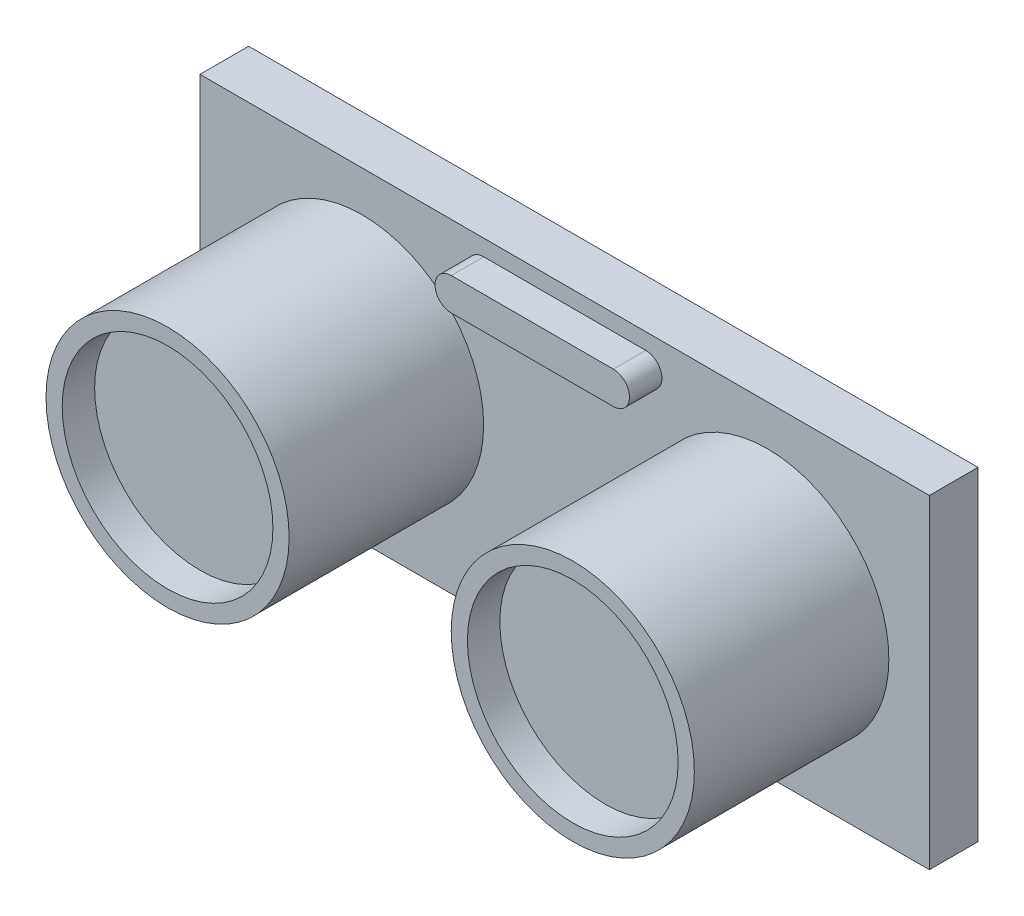
SolidWorks part; units mm, degrees
ref_plane "Front Plane" through (0, 0, 0) normal (0, 0, 1) x (1, 0, 0)
ref_plane "Top Plane" through (0, 0, 0) normal (0, 1, 0) x (1, 0, 0)
ref_plane "Right Plane" through (0, 0, 0) normal (1, 0, 0) x (0, 0, -1)
sketch "Sketch1" plane through (0, 0, 0) normal (0, 0, 1) x (1, 0, 0)
  line L1 (0, 0) -> (45, 0)
  line L2 (0, 0) -> (0, 20)
  line L3 (0, 20) -> (45, 20)
  line L4 (45, 0) -> (45, 20)
  dimension "D1" = 45
  dimension "D2" = 20
extrude "Boss-Extrude1" add sketch "Sketch1" along normal blind 3
sketch "Sketch2" plane through (0, 0, 3) normal (0, 0, 1) x (1, 0, 0)
  line L0 (45, 0) -> (45, 20) construction
  circle A0 centre (10, 10) radius 7.5
  circle A1 centre (35, 10) radius 7.5
  circle A2 centre (10, 10) radius 6.5
  circle A3 centre (35, 10) radius 6.5
  dimension "D3" = 15
  dimension "D4" = 15
  dimension "D6" = 13
  dimension "D7" = 13
  dimension "D1" = 10
  dimension "D2" = 10
  dimension "D5" = 10
extrude "Boss-Extrude2" add sketch "Sketch2" along normal blind 12
extrude "Boss-Extrude3" add sketch "Sketch2<2>" along normal blind 10 contours A2 | A3 region at (10, 10, 3) region at (35, 10, 3)
sketch "Sketch2<2>" plane through (0, 0, 3) normal (0, 0, 1) x (1, 0, 0) same geometry as "Sketch2"
sketch "Sketch3" plane through (0, 0, 3) normal (0, 0, 1) x (1, 0, 0)
  line L0 (17.5, 18) -> (27.5, 18) construction
  line L1 (17.5, 19) -> (27.5, 19)
  line L2 (17.5, 17) -> (27.5, 17)
  line L3 (45, 20) -> (0, 20) construction
  arc A0 (17.5, 19) -> (17.5, 17) centre (17.5, 18) ccw
  arc A1 (27.5, 17) -> (27.5, 19) centre (27.5, 18) ccw
  point P2 (22.5, 18)
  dimension "D1" = 22.5
  dimension "D2" = 10
  dimension "D3" = 2
  dimension "D4" = 2
extrude "Boss-Extrude4" add sketch "Sketch3" along normal blind 2
